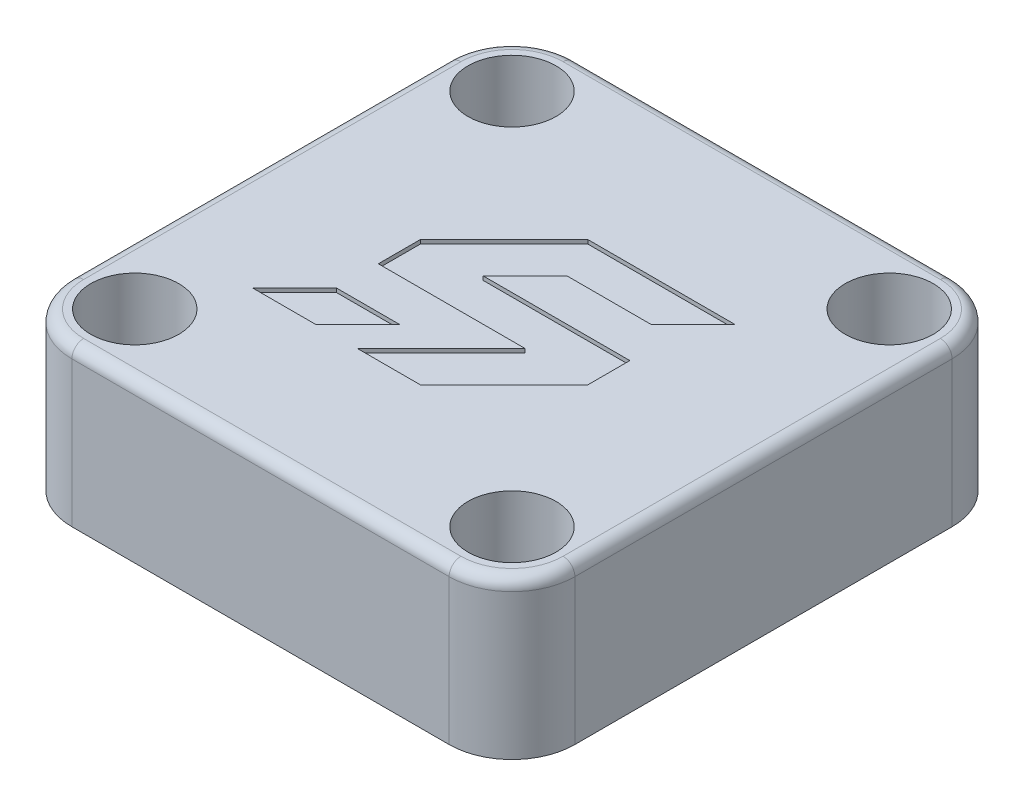
SolidWorks part; units mm, degrees
ref_plane "Front Plane" through (0, 0, 0) normal (0, 0, 1) x (1, 0, 0)
ref_plane "Top Plane" through (0, 0, 0) normal (0, 1, 0) x (1, 0, 0)
ref_plane "Right Plane" through (0, 0, 0) normal (1, 0, 0) x (0, 0, -1)
sketch "Sketch1" plane through (0, 0, 0) normal (0, 1, 0) x (1, 0, 0)
  line L0 (-16, 12) -> (-16, -12)
  line L1 (-12, 12) -> (12, 12)
  line L2 (-12, 12) -> (-12, -12)
  line L3 (-12, -12) -> (12, -12)
  line L4 (12, 12) -> (12, -12)
  line L5 (-12, 12) -> (12, -12) construction
  line L6 (-12, -12) -> (12, 12) construction
  line L7 (-12, -16) -> (12, -16)
  line L8 (16, 12) -> (16, -12)
  line L9 (-12, 16) -> (12, 16)
  circle A0 centre (-12, 12) radius 1.6
  circle A1 centre (12, 12) radius 1.6
  circle A2 centre (12, -12) radius 1.6
  circle A3 centre (-12, -12) radius 1.6
  circle A4 centre (-12, 12) radius 4
  circle A5 centre (12, 12) radius 4
  circle A6 centre (12, -12) radius 4
  circle A7 centre (-12, -12) radius 4
  point P0 (0, 0)
  dimension "D2" = 3.2
  dimension "D3" = 8
  dimension "D1" = 24
extrude "Boss-Extrude1" add sketch "Sketch1" along normal blind 10 contours A5 L9 A4 L1 | L1 A4 L2 A0 | A7 L2 A4 L0 | A7 L3 A3 L2 | A7 L7 A6 L3 | A6 L4 A2 L3 | A6 L8 A5 L4 | A7 L3 A6 L4 A5 L1 A4 L2 | L4 A6 L3 A2 | L3 A7 L2 A3 | L2 A4 L1 A0 | L4 A5 L1 A1 | L1 A5 L4 A1 region at (-14.1072, 0, 0) region at (-14.7484, 0, -14.7484) region at (-14.7484, 0, 9.2516) region at (0, 0, -14.1072) region at (0, 0, 0) region at (-10.1083, 0, -10.1083) region at (0, 0, 14.1072) region at (-10.1083, 0, 10.1083) region at (14.7484, 0, -14.7484) region at (9.2516, 0, 14.7484) region at (14.1072, 0, 0) region at (10.1083, 0, -10.1083) region at (10.1083, 0, 10.1083)
sketch "Sketch2" plane through (0, 0, 0) normal (0, -1, 0) x (1, 0, 0)
  line L0 (-12, 16) -> (12, 16) construction
  line L1 (8, -16) -> (-8, -16)
  line L2 (8, -16) -> (8, 16)
  line L3 (8, 16) -> (-8, 16)
  line L4 (-8, -16) -> (-8, 16)
  line L5 (8, -16) -> (-8, 16) construction
  line L6 (8, 16) -> (-8, -16) construction
  circle A0 centre (0, 0) radius 14
  circle A3 centre (-12, 12) radius 1.6 construction
  circle A4 centre (-12, 12) radius 1.6
  line M12 (-12, -16) -> (12, -16)
  dimension "D1" = 28
  dimension "D2" = 4
extrude "Cut-Extrude1" cut sketch "Sketch2" against normal offset from surface (8.5 mm away) 1.5 contours A0 L4 L2 M12 | A0 region at (0, 0, -14.5009) up to face at (-12, 10, 13.6)
sketch "Sketch3" plane through (0, 10, 0) normal (0, 1, 0) x (1, 0, 0)
  circle A0 centre (-12, 12) radius 2.8
  circle A1 centre (12, 12) radius 2.8
  circle A2 centre (12, -12) radius 2.8
  circle A3 centre (-12, -12) radius 2.8
  dimension "D1" = 5.6
extrude "Cut-Extrude2" cut sketch "Sketch3" against normal offset from surface (8 mm away) 2 up to face at (0, 0, -2.4574)
fillet "Fillet1" radius 3 2 edges at (-8, 4.25, -11.4891) (8, 4.25, -11.4891)
fillet "Fillet2" radius 3 5 edges at (8, 8.5, -14.4807) (8.2775, 8.5, -11.7012) (-8, 8.5, -14.4807) (-8.2775, 8.5, -11.7012) (0, 8.5, 14)
fillet "Fillet3" radius 0.75 8 edges at (-14.8284, 10, 14.8284) (-16, 10, 0) (-14.8284, 10, -14.8284) (0, 10, -16) (14.8284, 10, -14.8284) (16, 10, 0) (14.8284, 10, 14.8284) (0, 10, 16)
sketch "Sketch6" plane through (0, 10, 0) normal (0, 1, 0) x (1, 0, 0)
  line L0 (14.5917, 6.2385) -> (-1.4083, 6.2385)
  line L1 (14.5917, 6.2385) -> (1.2584, -7.0948)
  line L2 (11.9251, 3.5718) -> (-4.0749, 3.5718)
  line L3 (9.2584, 0.9052) -> (-6.7416, 0.9052)
  line L4 (6.5917, -1.7615) -> (-9.4083, -1.7615)
  line L5 (3.9251, -4.4282) -> (-12.0749, -4.4282)
  line L6 (1.2584, -7.0948) -> (-14.7416, -7.0948)
  line L7 (10.5917, 6.2385) -> (-2.7416, -7.0948)
  line L8 (6.5917, 6.2385) -> (-6.7416, -7.0948)
  line L9 (2.5917, 6.2385) -> (-10.7416, -7.0948)
  line L10 (-1.4083, 6.2385) -> (-14.7416, -7.0948)
  line L11 (-6.7416, 0.9052) -> (-6.7416, -1.7615)
  line L12 (6.5917, -1.7615) -> (6.5917, 0.9052)
  line L13 (-6.7416, -1.7615) -> (-6.7416, -4.4282) construction
  line L14 (-6.7416, -4.4282) -> (-9.4083, -7.0948)
  line L15 (-2.7416, -4.4282) -> (-5.4083, -7.0948)
  line L16 (-4.0749, -5.7615) -> (-8.0749, -5.7615) construction
  line L17 (-1.4083, -5.7615) -> (2.5917, -5.7615) construction
  line L18 (5.2584, 3.5718) -> (7.9251, 6.2385)
  dimension "D1" = 16
  dimension "D2" = 45
  dimension "D4" = 2.6667
  dimension "D3" = 6
  dimension "D5" = 5
extrude "Cut-Extrude3" cut sketch "Sketch6" against normal blind 0.25 contours L5 L14 L6 L8 | L15 L5 L8 L6 | L5 L7 L6 L1 | L4 L7 L5 L1 | L4 L12 L3 L7 | L3 L8 L4 L7 | L3 L9 L4 L8 | L3 L11 L4 L9 | L2 L10 L3 L9 | L0 L10 L2 L9 | L0 L9 L2 L8 | L2 L18 L0 L8 region at (5.9251, 10, -4.9052) region at (3.2584, 10, -4.9052) region at (1.9251, 10, 0.4282) region at (5.1473, 10, 0.6504) region at (3.2584, 10, 3.0948) region at (-0.7416, 10, -4.9052) region at (-2.0749, 10, 0.4282) region at (0.5917, 10, 5.7615) region at (-3.4083, 10, -2.2385) region at (-5.2972, 10, 0.206) region at (-6.7416, 10, 5.7615) region at (-4.7416, 10, 5.7615)
equation "\"D4@Sketch6\"=16/6"
